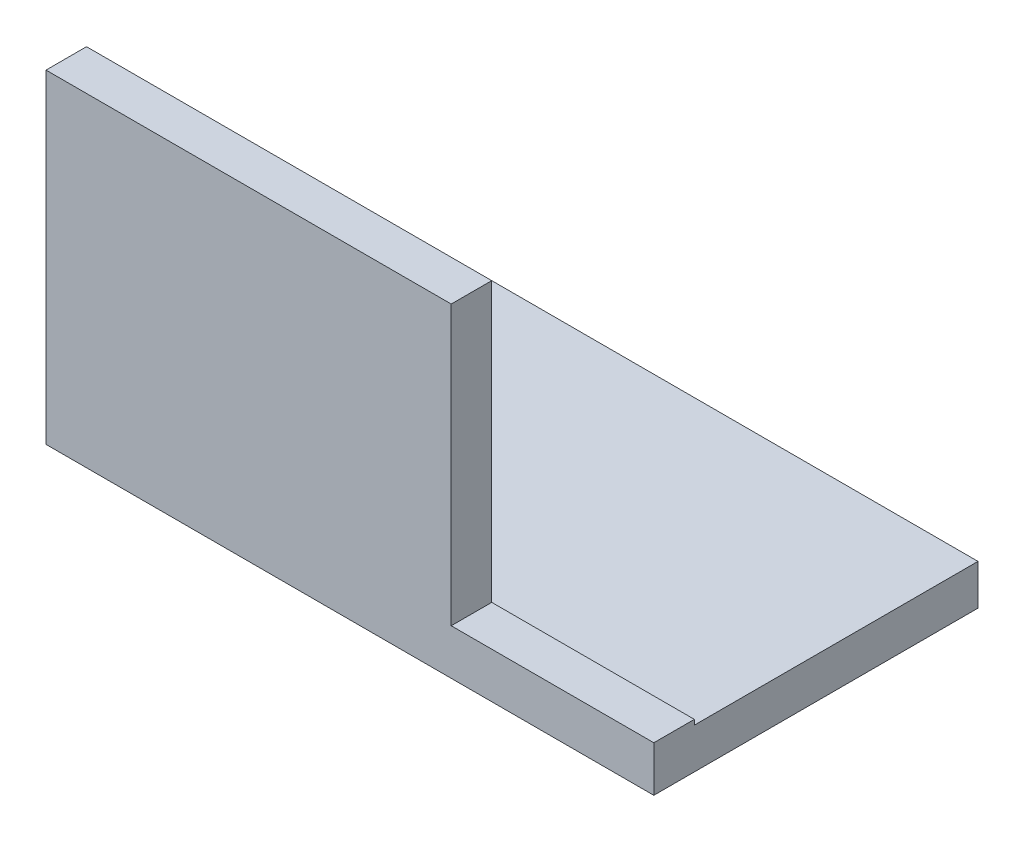
SolidWorks part; units mm, degrees
ref_plane "Спереди" through (0, 0, 0) normal (0, 0, 1) x (1, 0, 0)
ref_plane "Сверху" through (0, 0, 0) normal (0, 1, 0) x (1, 0, 0)
ref_plane "Справа" through (0, 0, 0) normal (1, 0, 0) x (0, 0, -1)
sketch "Эскиз1" plane through (0, 0, 0) normal (1, 0, 0) x (0, 0, -1)
  line L0 (0, 0) -> (32, 0)
  line L1 (0, 0) -> (0, 32)
extrude "Вытянуть-Тонкостенный1" add sketch "Эскиз1" along normal blind 60 thin thin type one direction wall 4
sketch "Эскиз2" plane through (0, 0, 0) normal (0, 0, 1) x (1, 0, 0)
  line L0 (60, 0) -> (60, 32) construction
  line L1 (40, 32) -> (60, 32)
  line L2 (40, 32) -> (40, 4.4951)
  line L3 (40, 4.4951) -> (60, 4.4951)
  line L4 (60, 32) -> (60, 4.4951)
  line L5 (60, 32) -> (0, 32) construction
extrude "Вырез-Вытянуть1" cut sketch "Эскиз2" against normal through all
